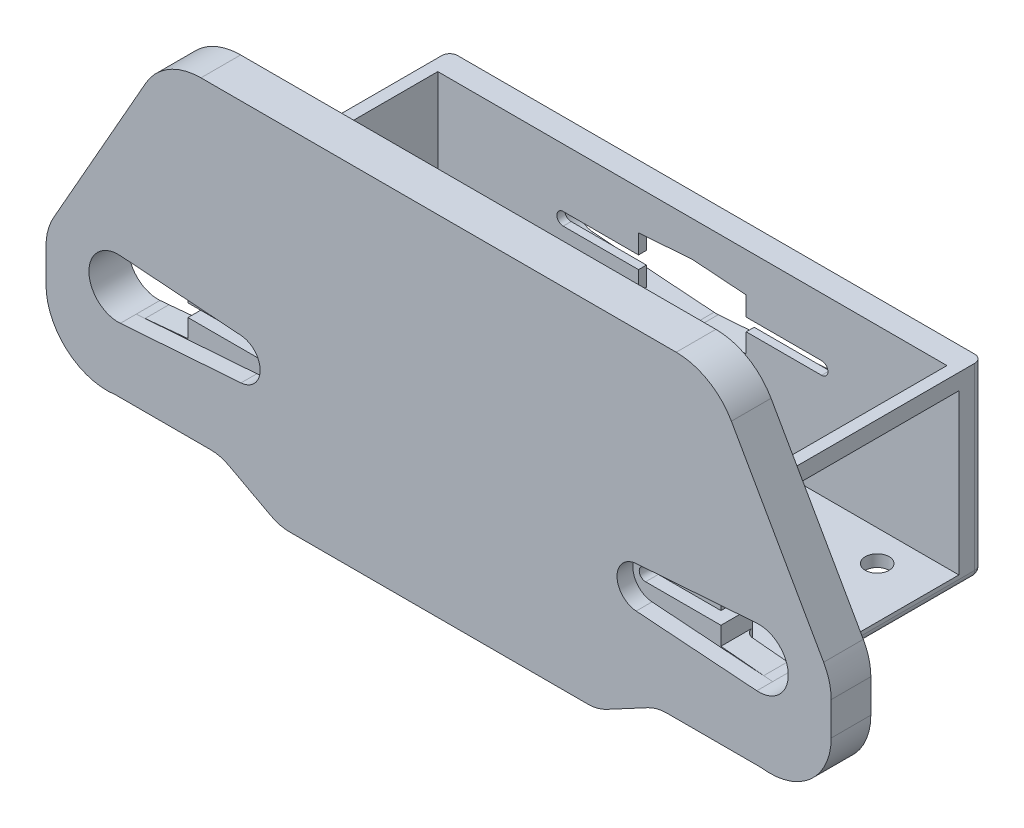
SolidWorks part; units mm, degrees
ref_plane "Front Plane" through (0, 0, 0) normal (0, 0, 1) x (1, 0, 0)
ref_plane "Top Plane" through (0, 0, 0) normal (0, 1, 0) x (1, 0, 0)
ref_plane "Right Plane" through (0, 0, 0) normal (1, 0, 0) x (0, 0, -1)
ref_plane "Plane1" through (0, 0, 0) normal (0, 0, -1) x (-1, 0, 0)
sketch "Sketch1" plane through (0, 0, 0) normal (0, 0, -1) x (-1, 0, 0)
  line L0 (0, 24.557) -> (0, -19.443) construction
  line L1 (-39, -0.0372) -> (-33.6, -0.5422)
  line L2 (-39, -3.6372) -> (-14.6934, -3.6372) construction
  line L3 (-33.6, -0.5422) -> (-33.6, -6.7322)
  line L4 (-33.6, -6.7322) -> (-39, -7.2372)
  line L5 (39, -0.0372) -> (33.6, -0.5422)
  line L6 (33.6, -0.5422) -> (33.6, -6.7322)
  line L7 (33.6, -6.7322) -> (39, -7.2372)
  line L28 (48.5487, 0) -> (36.9192, 20.5038)
  line L29 (29.9606, 24.557) -> (-29.9606, 24.557)
  line L30 (-36.9192, 20.5038) -> (-48.5487, 0)
  line L31 (-49.5, -3.6057) -> (-49.5, -7.8056)
  line L32 (-40.7247, -15.443) -> (-28.7691, -15.443)
  line L33 (-26.4102, -16.0345) -> (-21.1454, -18.8516)
  line L34 (-18.7864, -19.443) -> (18.7864, -19.443)
  line L35 (21.1454, -18.8516) -> (26.4102, -16.0345)
  line L36 (28.7691, -15.443) -> (40.7247, -15.443)
  line L37 (49.5, -7.8056) -> (49.5, -3.6057)
  line L38 (39, -3.6372) -> (39, -14.3112) construction
  line L39 (39, -3.6372) -> (31.4479, -3.6372) construction
  circle A5 centre (-39, -3.6372) radius 4 construction
  circle A7 centre (41.5, -8.6372) radius 0.75 construction
  circle A8 centre (36.5, -8.6372) radius 0.75 construction
  circle A9 centre (41.5, 1.3628) radius 0.75 construction
  circle A10 centre (39, -3.6372) radius 4 construction
  arc A11 (-39, -0.0372) -> (-39, -7.2372) centre (-39, -3.6372) ccw
  arc A12 (39, -0.0372) -> (39, -7.2372) centre (39, -3.6372) cw
  circle A15 centre (36.5, 1.3628) radius 0.75 construction
  arc A19 (49.5, -3.6057) -> (48.5487, 0) centre (42.1915, -3.6057) ccw
  arc A20 (36.9192, 20.5038) -> (29.9606, 24.557) centre (29.9606, 16.557) ccw
  arc A21 (-29.9606, 24.557) -> (-36.9192, 20.5038) centre (-29.9606, 16.557) ccw
  arc A22 (-48.5487, 0) -> (-49.5, -3.6057) centre (-42.1915, -3.6057) ccw
  arc A23 (-49.5, -7.8056) -> (-40.7247, -15.443) centre (-41.7888, -7.8056) ccw
  arc A24 (-28.7691, -15.443) -> (-26.4102, -16.0345) centre (-28.7691, -20.443) cw
  arc A25 (-21.1454, -18.8516) -> (-18.7864, -19.443) centre (-18.7864, -14.443) ccw
  arc A26 (18.7864, -19.443) -> (21.1454, -18.8516) centre (18.7864, -14.443) ccw
  arc A27 (26.4102, -16.0345) -> (28.7691, -15.443) centre (28.7691, -20.443) cw
  arc A28 (40.7247, -15.443) -> (49.5, -7.8056) centre (41.7888, -7.8056) ccw
  dimension "D2" = 8
  dimension "D4" = 7.3085
  dimension "D6" = 7.7112
  dimension "D8" = 5
  dimension "D10" = 5
  dimension "D12" = 5
  dimension "D14" = 5
  dimension "D16" = 7.7112
  dimension "D18" = 7.3085
  dimension "D20" = 8
  dimension "D27" = 8
  dimension "D28" = 1.5
  dimension "D29" = 7.2
  dimension "D31" = 9
  dimension "D1" = 59.9212
  dimension "D3" = 20.5038
  dimension "D5" = 4.1999
  dimension "D7" = 11.9556
  dimension "D9" = 5.9711
  dimension "D11" = 37.5729
  dimension "D13" = 5.9711
  dimension "D15" = 11.9556
  dimension "D17" = 4.1999
  dimension "D19" = 20.5038
  dimension "D21" = 10.5
  dimension "D22" = 5
  dimension "D23" = 5
  dimension "D24" = 11.8058
  dimension "D25" = 4
  dimension "D26" = 44
  dimension "D30" = 6.19
extrude "Boss-Extrude1" add sketch "Sketch1" against normal blind 5
sketch "Sketch7" plane through (0, 0, 5) normal (0, 0, 1) x (1, 0, 0)
  line L0 (-40.1238, 0.0532) -> (-24.9129, -1.044)
  line L2 (-40.1238, -7.3276) -> (-24.9129, -6.2305)
  arc A1 (-40.1238, 0.0532) -> (-40.1238, -7.3276) centre (-40.39, -3.6372) ccw
  arc A2 (-24.9129, -1.044) -> (-24.9129, -6.2305) centre (-25.1, -3.6372) cw
  circle A3 centre (-39, -3.6372) radius 3.6 construction
  arc A4 (-39, -0.0372) -> (-39, -7.2372) centre (-39, -3.6372) ccw construction
  point P2 (0, 0)
  dimension "D1" = 3.7
  dimension "D2" = 2.6
  dimension "D3" = 16.5
extrude "Cut-Extrude2" cut sketch "Sketch7" against normal offset from surface (2 mm away) 3 up to face at (37.2, -3.6372, 0)
sketch "Sketch8" plane through (0, 0, 3) normal (0, 0, 1) x (1, 0, 0)
  line L0 (-40.1238, 0.0532) -> (-39, -0.0372)
  line L1 (-40.1238, -7.3276) -> (-39, -7.2372)
  line L2 (-40.1238, -7.3276) -> (-24.9129, -6.2305)
  line L3 (-24.9129, -1.044) -> (-40.1238, 0.0532)
  arc A0 (-39, -0.0372) -> (-39, -7.2372) centre (-39, -3.6372) ccw construction
  arc A1 (-39, -0.0372) -> (-39, -7.2372) centre (-39, -3.6372) ccw
  arc A2 (-40.1238, 0.0532) -> (-40.1238, -7.3276) centre (-40.39, -3.6372) ccw
  arc A3 (-24.9129, -6.2305) -> (-24.9129, -1.044) centre (-25.1, -3.6372) ccw
  arc A4 (-40.1238, 0.0532) -> (-40.1238, -7.3276) centre (-40.39, -3.6372) ccw
  dimension "D1" = 0
extrude "Cut-Extrude3" cut sketch "Sketch8" against normal through all
sketch "Sketch9" plane through (0, 0, 3) normal (0, 0, 1) x (1, 0, 0)
  line L0 (-44.09, -3.6372) -> (-22.5, -3.6372) construction
  line L2 (-24.1, -2.8372) -> (-33.6, -2.8372)
  line L3 (-33.6, -6.7322) -> (-33.6, -0.5422) construction
  line L4 (-33.6, -2.8372) -> (-33.6, -4.4372)
  line L5 (-33.6, -4.4372) -> (-24.1, -4.4372)
  arc A0 (-40.1238, 0.0532) -> (-40.1238, -7.3276) centre (-40.39, -3.6372) ccw construction
  arc A1 (-24.9129, -6.2305) -> (-24.9129, -1.044) centre (-25.1, -3.6372) ccw construction
  circle A3 centre (-24.1, -3.6372) radius 0.8 construction
  arc A4 (-24.1, -2.8372) -> (-24.1, -4.4372) centre (-24.1, -3.6372) cw
  dimension "D1" = 1.6
  dimension "D2" = 0.8
extrude "Cut-Extrude4" cut sketch "Sketch9" against normal through all
mirror "Mirror1" about plane through (0, 0, 0) normal (1, 0, 0) of "Cut-Extrude4", "Cut-Extrude3", "Cut-Extrude2"
sketch "Sketch12" plane through (0, 0, 0) normal (0, 0, -1) x (-1, 0, 0)
  line L0 (-40.39, -3.6372) -> (40.39, -3.6372) construction
  line L1 (-33.6, -2.8372) -> (-33.6, -0.5422) construction
  line L2 (33.6, -15.443) -> (-33.6, -15.443)
  line L3 (33.6, -15.443) -> (33.6, 8.1686)
  line L4 (33.6, 8.1686) -> (-33.6, 8.1686)
  line L5 (-33.6, -15.443) -> (-33.6, 8.1686)
  line L6 (33.6, -15.443) -> (-33.6, 8.1686) construction
  line L7 (33.6, 8.1686) -> (-33.6, -15.443) construction
  line L8 (-40.7247, -15.443) -> (-28.7691, -15.443) construction
  point P4 (0, -3.6372)
extrude "Boss-Extrude2" add sketch "Sketch12" along normal blind 30
sketch "Sketch13" plane through (0, 8.1686, 0) normal (0, 1, 0) x (1, 0, 0)
  line L1 (32.1, 0) -> (-32.1, 0)
  line L2 (32.1, 0) -> (32.1, 27)
  line L3 (32.1, 27) -> (-32.1, 27)
  line L4 (-32.1, 0) -> (-32.1, 27)
  line L5 (32.1, 0) -> (-32.1, 27) construction
  line L6 (32.1, 27) -> (-32.1, 0) construction
  line L7 (-29.9606, 0) -> (29.9606, 0) construction
  line L8 (-33.6, 30) -> (-33.6, 0) construction
  line L9 (33.6, 30) -> (33.6, 0) construction
  point P0 (0, 13.5)
  dimension "D1" = 27
  dimension "D2" = 1.5
  dimension "D3" = 1.5
extrude "Cut-Extrude5" cut sketch "Sketch13" against normal offset from surface (22.1116 mm away) 1.5 up to face at (0, -15.443, -3.3333)
fillet "Fillet1" radius 1 10 edges at (-37.1623, -15.443, 0) (33.6, 3.8132, 0) (33.6, -11.0876, 0) (33.6, -15.443, -15) (-33.6, -11.0876, 0) (-33.6, -15.443, -15) (33.6, -3.6372, -30) (0, -15.443, -30) (-33.6, -3.6372, -30) (37.1623, -15.443, 0)
fillet "Fillet2" radius 4 7 edges at (-27.5531, -15.5931, 0) (-23.7778, -17.443, 0) (-20.0024, -19.2929, 0) (0, -15.443, 0) (20.0024, -19.2929, 0) (23.7778, -17.443, 0) (27.5531, -15.5931, 0)
sketch "Sketch14" plane through (0, -13.943, 0) normal (0, 1, 0) x (1, 0, 0)
  line L0 (0, 0) -> (0, 27) construction
  line L1 (-32.1, 0) -> (32.1, 0) construction
  line L2 (32.1, 27) -> (-32.1, 27) construction
  line L3 (0, 13.5) -> (-32.1, 13.5) construction
  line L4 (-32.1, 27) -> (-32.1, 0) construction
  circle A0 centre (27.2, 23.1) radius 1.5
  circle A1 centre (-27.2, 23.1) radius 1.5
  circle A2 centre (27.2, 3.9) radius 1.5
  circle A3 centre (-27.2, 3.9) radius 1.5
  dimension "D1" = 3
  dimension "D2" = 16.2
  dimension "D3" = 52.9
extrude "Cut-Extrude6" cut sketch "Sketch14" against normal through all
sketch "Sketch15" plane through (33.6, 0, 0) normal (1, 0, 0) x (0, 0, -1)
  line L0 (29, 8.1686) -> (1, 8.1686) construction
  line L1 (1, 6.1686) -> (27, 6.1686)
  line L2 (1, 6.1686) -> (1, -13.943)
  line L3 (1, -13.943) -> (27, -13.943)
  line L4 (27, 6.1686) -> (27, -13.943)
  line L5 (1, 6.1686) -> (27, -13.943) construction
  line L6 (1, -13.943) -> (27, 6.1686) construction
  line L7 (29, -15.443) -> (1, -15.443) construction
  line L8 (0, -0.4487) -> (0, 8.1686) construction
  point P0 (14, -3.8872)
  point P5 (0, 0)
  dimension "D1" = 1
  dimension "D2" = 2
  dimension "D3" = 1.5
extrude "Cut-Extrude7" cut sketch "Sketch15" against normal up to next
sketch "Sketch16" plane through (0, 0, -30) normal (0, 0, -1) x (-1, 0, 0)
  line L0 (-40.39, -3.6372) -> (40.39, -3.6372) construction
  line L1 (0.2662, 3.6904) -> (15.4771, 2.5933)
  line L2 (0.2662, -3.6904) -> (15.4771, -2.5933)
  arc A0 (0.2662, 3.6904) -> (0.2662, -3.6904) centre (0, 0) ccw
  arc A1 (15.4771, 2.5933) -> (15.4771, -2.5933) centre (15.29, 0) cw
  circle A2 centre (1.39, 0) radius 3.6 construction
  point P12 (0, 0)
  point P13 (-14.5586, 0.8669)
  point P14 (0, 0)
  point P15 (-14.2609, -8.258)
  point P16 (0.8316, 0)
  point P17 (0, 0)
  point P18 (0, 0)
  point P19 (0.0498, 0.231)
  dimension "D1" = 3.7
  dimension "D3" = 2.6
  dimension "D4" = 7.2
  dimension "D2" = 16.5
extrude "Cut-Extrude8" cut sketch "Sketch16" against normal blind 2
sketch "Sketch19" plane through (0, 0, -28) normal (0, 0, -1) x (-1, 0, 0)
  line L0 (6.79, 0.8) -> (16.29, 0.8)
  line L1 (16.29, -0.8) -> (6.79, -0.8)
  line L2 (6.79, -0.8) -> (6.79, 0.8)
  line L3 (0, 0) -> (6.79, 0) construction
  arc A0 (16.29, 0.8) -> (16.29, -0.8) centre (16.29, 0) cw
  arc A3 (15.4771, -2.5933) -> (15.4771, 2.5933) centre (15.29, 0) ccw construction
  circle A4 centre (16.29, 0) radius 0.8 construction
  dimension "D2" = 1.6
  dimension "D3" = 0.8
  dimension "D1" = 9.5
extrude "Cut-Extrude9" cut sketch "Sketch19" against normal up to surface (1 mm away) up to face at (11.2, 0.1314, -27)
sketch "Sketch20" plane through (0, 0, -28) normal (0, 0, -1) x (-1, 0, 0)
  line L0 (6.79, 3.2199) -> (6.79, -3.2199)
  line L2 (0.2662, -3.6904) -> (15.4771, -2.5933)
  line L3 (15.4771, 2.5933) -> (0.2662, 3.6904)
  line L4 (0.2662, -3.6904) -> (6.79, -3.2199)
  line L5 (6.79, 3.2199) -> (0.2662, 3.6904)
  arc A2 (0.2662, 3.6904) -> (0.2662, -3.6904) centre (0, 0) ccw
  arc A3 (15.4771, -2.5933) -> (15.4771, 2.5933) centre (15.29, 0) ccw
  arc A4 (0.2662, 3.6904) -> (0.2662, -3.6904) centre (0, 0) ccw
  dimension "D1" = 0
extrude "Cut-Extrude10" cut sketch "Sketch20" against normal up to surface (1 mm away) up to face at (-11.74, 0, -27)
mirror "Mirror2" about plane through (0, 0, 0) normal (1, 0, 0) of "Cut-Extrude8", "Cut-Extrude10", "Cut-Extrude9"
